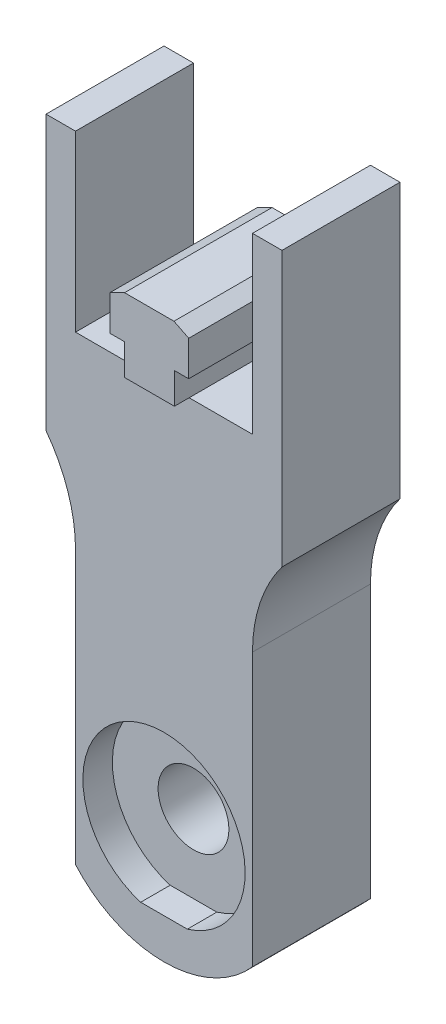
SolidWorks part; units mm, degrees
ref_plane "Front Plane" through (0, 0, 0) normal (0, 0, 1) x (1, 0, 0)
ref_plane "Top Plane" through (0, 0, 0) normal (0, 1, 0) x (1, 0, 0)
ref_plane "Right Plane" through (0, 0, 0) normal (1, 0, 0) x (0, 0, -1)
sketch "Sketch1" plane through (0, 0, 0) normal (0, 0, 1) x (1, 0, 0)
  line L0 (-2.695, 0.5997) -> (-1.695, 1.0997)
  line L1 (-2.695, -1.7803) -> (-1.715, -1.7803)
  line L2 (-2.695, -1.7803) -> (-2.695, 0.5997)
  line L3 (-1.695, 1.0997) -> (1.655, 1.0997)
  line L4 (2.655, -1.7803) -> (2.655, 0.5997)
  line L7 (2.655, 0.5997) -> (1.655, 1.0997)
  line L8 (1.685, -1.7803) -> (2.655, -1.7803)
  line L10 (-1.715, -1.7803) -> (-1.715, -3.8803)
  line L11 (-1.715, -3.8803) -> (1.685, -3.8803)
  line L12 (1.685, -1.7803) -> (1.685, -3.8803)
  point P0 (0, 0)
  dimension "D1" = 5.35
  dimension "D2" = 3.4
  dimension "D3" = 2.1
  dimension "2.38" = 2.38
  dimension "D5" = 2.38
  dimension "D6" = 0.5
  dimension "D7" = 1
  dimension "D8" = 1
  dimension "D9" = 0.97
extrude "Boss-Extrude1" add sketch "Sketch1" along normal blind 10
sketch "Sketch3" plane through (0, -3.8803, 0) normal (0, -1, 0) x (1, 0, 0)
  line L0 (-1.695, 10) -> (1.655, 0)
  line L2 (-6.02, 3) -> (5.98, 3)
  line L3 (-6.02, 3) -> (-6.02, 7)
  line L4 (-6.02, 7) -> (5.98, 7)
  line L5 (5.98, 3) -> (5.98, 7)
  line L6 (-6.02, 3) -> (5.98, 7) construction
  line L7 (-6.02, 7) -> (5.98, 3) construction
  point P4 (-0.02, 5)
  line M6 (1.685, 0) -> (1.685, 10)
  line M8 (-1.715, 10) -> (-1.715, 0)
  dimension "D1" = 12
  dimension "D2" = 4
extrude "Boss-Extrude2" add sketch "Sketch3" along normal blind 36 contours L4 L3 L2 M8 | L4 L2 L0 M8 | L4 L0 L2 M6 | L2 L5 L4 M6 region at (0.7886, -3.8803, 5.262) region at (-0.8234, -3.8803, 4.7365) region at (-3.8675, -3.8803, 5) region at (3.8325, -3.8803, 5)
sketch "Sketch4" plane through (0, 0, 7) normal (0, 0, 1) x (1, 0, 0)
  line L0 (-6.02, -3.8803) -> (-1.715, -3.8803) construction
  line L1 (5.98, -39.8803) -> (5.98, -3.8803) construction
  line L2 (5.98, -21.8803) -> (-6.02, -37.8803) construction
  line L3 (-6.02, -39.8803) -> (-6.02, -3.8803) construction
  circle A0 centre (-0.02, -29.8803) radius 2.4
  dimension "D1" = 4.8
  dimension "D2" = 26
extrude "Cut-Extrude1" cut sketch "Sketch4" against normal blind 8
sketch "Sketch6" plane through (0, 0, 7) normal (0, 0, 1) x (1, 0, 0)
  line L10 (-1.715, -3.8803) -> (-6.02, -3.8803)
  line L11 (-6.02, -3.8803) -> (-6.02, -39.8803)
  line L12 (-6.02, -39.8803) -> (5.98, -39.8803)
  line L13 (5.98, -39.8803) -> (5.98, -3.8803)
  line L14 (5.98, -3.8803) -> (1.685, -3.8803)
  line L15 (1.685, -3.8803) -> (-1.715, -3.8803)
  line L18 (-1.715, -3.8803) -> (-6.02, -3.8803)
  line L19 (-6.02, -3.8803) -> (-6.02, -39.8803)
  line L20 (-6.02, -39.8803) -> (5.98, -39.8803)
  line L21 (5.98, -39.8803) -> (5.98, -3.8803)
  line L22 (5.98, -3.8803) -> (1.685, -3.8803)
  line L24 (1.685, -3.8803) -> (-1.715, -3.8803)
  circle A0 centre (-0.02, -29.8803) radius 5.5
  dimension "D2" = 11
  dimension "D1" = 0
extrude "Boss-Extrude7" add sketch "Sketch6" along normal blind 2
extrude "Boss-Extrude8" add sketch "Sketch6<2>" against normal blind 6
sketch "Sketch6<2>" plane through (0, 0, 7) normal (0, 0, 1) x (1, 0, 0) same geometry as "Sketch6"
sketch "Sketch9" plane through (0, -39.8803, 0) normal (0, -1, 0) x (1, 0, 0)
  line L0 (-6.02, 9) -> (5.98, 1) construction
  line L1 (5.98, 1) -> (-6.02, 1) construction
  line L2 (-6.02, 1) -> (5.98, 9) construction
  line L4 (-6.0437, -6.9972) -> (6.0037, -6.9972)
  line L5 (-6.0437, -6.9972) -> (-6.0437, 16.9972)
  line L6 (-6.0437, 16.9972) -> (6.0037, 16.9972)
  line L7 (6.0037, -6.9972) -> (6.0037, 16.9972)
  line L8 (-6.0437, -6.9972) -> (6.0037, 16.9972) construction
  line L9 (-6.0437, 16.9972) -> (6.0037, -6.9972) construction
  circle A0 centre (-0.04, 12) radius 2.5
  circle A1 centre (0, -2) radius 2.5
  point P4 (-0.02, 5)
  dimension "D1" = 5
  dimension "D2" = 5
  dimension "D3" = 14
  dimension "D4" = 7
  dimension "D5" = 7
extrude "Boss-Extrude10" add sketch "Sketch9" along normal blind 3
sketch "Sketch10" plane through (5.98, 0, 0) normal (1, 0, 0) x (0, 0, -1)
  line L0 (6.9972, -39.8803) -> (-16.9972, -39.8803) construction
  line L1 (6.9972, -39.8803) -> (-16.9972, -39.8803)
  line L3 (-9, -39.8803) -> (-8, -39.8803)
  line L4 (-9, -3.8803) -> (-9, -39.8803)
  line L5 (-9, -39.8803) -> (-1, -39.8803)
  line L6 (-1, -39.8803) -> (-1, -3.8803)
  line L7 (-1, -3.8803) -> (-9, -3.8803)
  line L8 (-9, -3.8803) -> (-9, -39.8803)
  line L9 (-9, -39.8803) -> (-1, -39.8803)
  line L10 (-1, -39.8803) -> (-1, -3.8803)
  line L11 (-1, -3.8803) -> (-9, -3.8803)
  line L12 (-9, -39.8803) -> (-9, -36.8803)
  line L13 (-9, -36.8803) -> (-8, -36.8803)
  line L14 (-8, -39.8803) -> (-8, -36.8803)
  line L15 (-1, -39.8803) -> (-2, -39.8803)
  line L16 (-1, -39.8803) -> (-1, -36.8803)
  line L17 (-1, -36.8803) -> (-2, -36.8803)
  line L18 (-2, -39.8803) -> (-2, -36.8803)
  line M10 (-9, -39.8803) -> (-1, -39.8803)
  line M11 (-1, -39.8803) -> (-1, -3.8803)
  dimension "D2" = 1
  dimension "D3" = 3
  dimension "D4" = 1
  dimension "D5" = 3
  dimension "D1" = 0
extrude "Cut-Extrude2" cut sketch "Sketch10" against normal up to surface (12 mm away) contours L14 L13 L8 M10 | L18 L9 L17 M11 region at (5.98, -38.3803, 1.5) region at (5.98, -38.3803, 8.5) up to face at (-6.02, -21.8803, 5)
fillet "Fillet1" radius 2 4 edges at (-0.02, -36.8803, 1) (-0.02, -39.8803, 2) (-0.02, -39.8803, 8) (-0.02, -36.8803, 9)
sketch "Sketch11" plane through (0, 0, 16.9972) normal (0, 0, 1) x (1, 0, 0)
  line L1 (10.1776, -46.8065) -> (-10.6517, -46.8065)
  line L2 (10.1776, -46.8065) -> (10.1776, -35.1482)
  line L3 (10.1776, -35.1482) -> (-10.6517, -35.1482)
  line L4 (-10.6517, -46.8065) -> (-10.6517, -35.1482)
extrude "Cut-Extrude4" cut sketch "Sketch11" against normal through all
sketch "Sketch12" plane through (0, 0, 9) normal (0, 0, 1) x (1, 0, 0)
  line L4 (-6.02, -35.1482) -> (5.98, -35.1482)
  line L7 (-6.02, -3.8803) -> (-6.02, -35.1482)
  line L8 (-6.02, -35.1482) -> (-1.6007, -35.1482)
  line L9 (1.5607, -35.1482) -> (5.98, -35.1482)
  line L10 (5.98, -35.1482) -> (5.98, -3.8803)
  line L11 (5.98, -3.8803) -> (1.685, -3.8803)
  line L12 (1.685, -3.8803) -> (-1.715, -3.8803)
  line L13 (-1.715, -3.8803) -> (-6.02, -3.8803)
  line L18 (5.98, -3.8803) -> (1.685, -3.8803)
  line L19 (1.685, -3.8803) -> (-1.715, -3.8803)
  line L20 (-1.715, -3.8803) -> (-6.02, -3.8803)
  arc A1 (1.5607, -35.1482) -> (-1.6007, -35.1482) centre (-0.02, -29.8803) ccw
  arc A3 (-6.02, -35.1482) -> (5.98, -35.1482) centre (-0.02, -29.8803) ccw
  line M10 (-6.02, -35.1482) -> (-1.6007, -35.1482)
  line M12 (1.5607, -35.1482) -> (5.98, -35.1482)
  dimension "D1" = 0
extrude "Boss-Extrude11" add sketch "Sketch12" along direction (0, 0, 1) on the side against the normal up to surface (8 mm away) contours A3 L4 M10 M12 region at (-0.02, -36.2524, 9) up to face at (-0.0188, -18.1683, 1)
sketch "Sketch13" plane through (-6.02, 0, 0) normal (-1, 0, 0) x (0, 0, 1)
  line L0 (1, -3.8803) -> (1, -35.1482) construction
  line L1 (1, -10.6666) -> (9, -10.6666)
  line L2 (1, -10.6666) -> (1, 7.9238)
  line L3 (1, 7.9238) -> (9, 7.9238)
  line L4 (9, -10.6666) -> (9, 7.9238)
extrude "Boss-Extrude12" add sketch "Sketch13" along normal blind 2
sketch "Sketch14" plane through (5.98, 0, 0) normal (1, 0, 0) x (0, 0, -1)
  line L0 (-1, -35.1482) -> (-1, -3.8803) construction
  line L1 (-9, 7.9238) -> (-1, 7.9238)
  line L2 (-9, 7.9238) -> (-9, -10.6703)
  line L3 (-9, -10.6703) -> (-1, -10.6703)
  line L4 (-1, 7.9238) -> (-1, -10.6703)
  line L5 (-1, -3.8803) -> (-9, -3.8803) construction
  dimension "D1" = 6.79
extrude "Boss-Extrude13" add sketch "Sketch14" along normal blind 2
fillet "Fillet2" radius 10 2 edges at (-6.02, -10.6666, 5) (5.98, -10.6703, 5)
